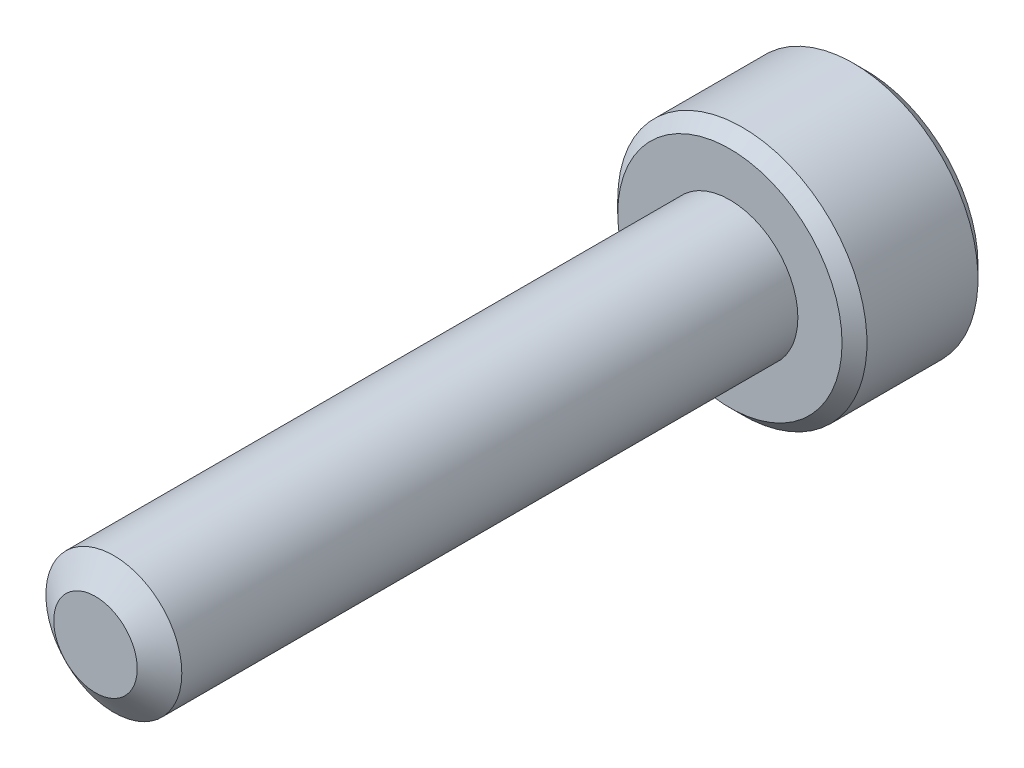
SolidWorks part; units mm, degrees
other "DetailItem1"
ref_plane "Front Plane" through (0, 0, 0) normal (0, 0, 1) x (1, 0, 0)
ref_plane "Top Plane" through (0, 0, 0) normal (0, 1, 0) x (1, 0, 0)
ref_plane "Right Plane" through (0, 0, 0) normal (1, 0, 0) x (0, 0, -1)
sketch "Sketch1" plane through (0, 0, 0) normal (0, 0, 1) x (1, 0, 0)
  circle A0 centre (0, 0) radius 1.5
  dimension "OD" = 3
extrude "Extrude1" add sketch "Sketch1" against normal blind 14
sketch "Sketch2" plane through (0, 0, 0) normal (0, 0, 1) x (1, 0, 0)
  circle A0 centre (0, 0) radius 1.5 construction
  circle A1 centre (0, 0) radius 1.5
curve "Helix/Spiral1" pitch 0.5 height 14.5 turns 29 parameters "pitch"=0.5
sketch "Sketch3" plane through (0, 0, 0) normal (1, 0, 0) x (0, 0, -1)
  line L0 (-0.4375, 1.5) -> (-0.25, 1.1752)
  line L1 (-0.25, 1.1752) -> (-0.1875, 1.1752)
  line L2 (-0.1875, 1.1752) -> (0, 1.5)
  line L3 (-0.4375, 1.5) -> (0, 1.5)
  line L4 (-0.2187, 1.5) -> (-0.2188, 1.1752) construction
  line L5 (-0.3438, 1.3376) -> (-0.0938, 1.3376) construction
  line L6 (0, 1.5) -> (0, -1.5) construction
  dimension "D1" = 0.0625
  dimension "D2" = 0.25
  dimension "D3" = 60
sweep "Cut-Sweep1" [suppressed] cut profiles "Sketch3" path "Helix/Spiral1"
sketch "Sketch4" plane through (0, 0, 0) normal (1, 0, 0) x (0, 0, -1)
  line L0 (0.4053, 1.5) -> (0, 0.9212)
  line L1 (0, 0.9212) -> (0, 1.5)
  line L2 (0.4053, 1.5) -> (0, 1.5)
  line L3 (-0.4375, 1.5) -> (0, 1.5) construction
  line L4 (0, 0) -> (7.0209, 0) construction
  dimension "D1" = 55
  dimension "D2" = 0.254
revolve "Cut-Revolve1" cut sketch "Sketch4" angle 360 about L4
sketch "Sketch6" plane through (0, 0, -14) normal (0, 0, -1) x (-1, 0, 0)
  circle A0 centre (0, 0) radius 2.75
  dimension "head dia" = 5.5
extrude "Extrude2" add sketch "Sketch6" along normal blind 3
sketch "Sketch7" plane through (0, 0, -17) normal (0, 0, -1) x (-1, 0, 0)
  line L1 (0, 1.4434) -> (-1.25, 0.7217)
  line L2 (-1.25, 0.7217) -> (-1.25, -0.7217)
  line L3 (-1.25, -0.7217) -> (0, -1.4434)
  line L4 (0, -1.4434) -> (1.25, -0.7217)
  line L5 (1.25, -0.7217) -> (1.25, 0.7217)
  line L6 (1.25, 0.7217) -> (0, 1.4434)
  circle A0 centre (0, 0) radius 1.25 construction
  dimension "hex dia" = 2.5
extrude "Cut-Extrude1" cut sketch "Sketch7" against normal blind 1.875
sketch "Sketch8" plane through (0, 0, -17) normal (0, 0, -1) x (-1, 0, 0)
  circle A0 centre (0, 0) radius 1.4434
extrude "Cut-Extrude2" cut sketch "Sketch8" against normal through all draft 45
chamfer "Chamfer1" distance 0.275 angle 45 2 edges at (-2.75, 0, -17) (-2.75, 0, -14)
sketch "Sketch10" plane through (0, 0, -14) normal (0, 0, 1) x (1, 0, 0)
  circle A1 centre (0, 0) radius 1.5
  circle A2 centre (0, 0) radius 1.5
  dimension "D1" = 0
ref_plane "Plane1" through (0, 0, 0) normal (0, 0, 1) x (1, 0, 0)
extrude "partial thread" [suppressed] add sketch "Sketch10" along normal up to surface (4 mm away) separate body up to plane "Plane1"
chamfer "Chamfer2" [suppressed] distance 0.06 angle 45
combine bodies "Combine1" [suppressed] operation type add bodies to combine 107 108
sketch "Sketch9" plane through (0, 0, 0) normal (1, 0, 0) x (0, 0, -1)
  line L0 (0, 1.5) -> (0, -1.5) construction
  line L1 (1.25, 1.5) -> (1.25, -1.5) construction
  dimension "D1" = 1.25
equation "\"D3@Helix/Spiral1\" = \"screw length@Extrude1\"+\"pitch@Helix/Spiral1\""
equation "\"D1@Sketch3\" = \"pitch@Helix/Spiral1\"*.125"
equation "\"D2@Sketch3\" = \"pitch@Helix/Spiral1\"*.5"
equation "\"D1@Cut-Extrude1\" = \"hex dia@Sketch7\"*.75"
equation "\"D1@Chamfer1\" = \"head dia@Sketch6\"*.05"
equation "\"D1@Sketch9\" = \"pitch@Helix/Spiral1\"*2.5"
equation "\"D1@Chamfer2\"=\"OD@Sketch1\"*.02"
